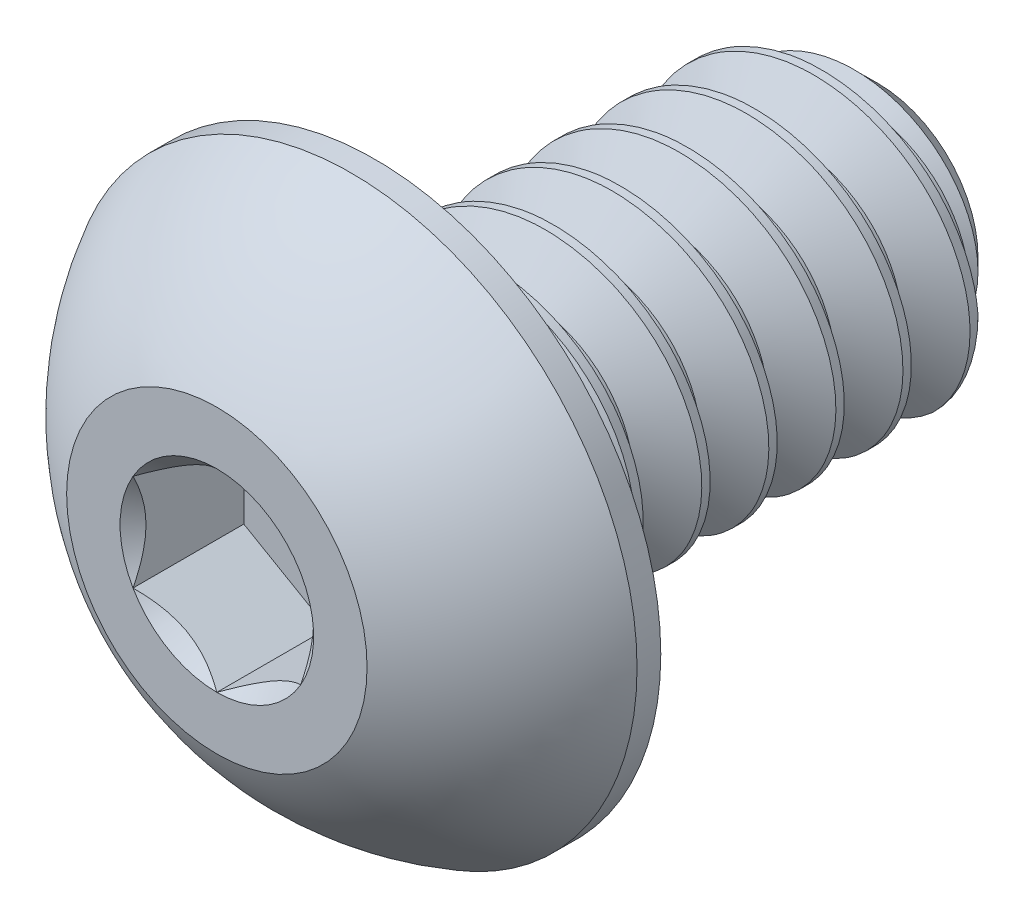
SolidWorks part; units mm, degrees
ref_plane "Front" through (0, 0, 0) normal (0, 0, 1) x (1, 0, 0)
ref_plane "Top" through (0, 0, 0) normal (0, 1, 0) x (1, 0, 0)
ref_plane "Right" through (0, 0, 0) normal (1, 0, 0) x (0, 0, -1)
sketch "Sketch1" plane through (0, 0, 0) normal (1, 0, 0) x (0, 0, -1)
  line L2 (1.4986, 1.4224) -> (6.2611, 1.4224)
  line L3 (6.2611, 1.4224) -> (6.2611, 0)
  line L4 (6.2611, 0) -> (1.4986, 0)
  line L6 (1.2738, 2.7051) -> (1.4986, 2.7051) construction
  line L7 (6.2611, 1.4224) -> (6.2611, -1.4224) construction
  line L8 (0, 0) -> (1.4986, 0) construction
  line L9 (1.4986, 2.7051) -> (1.4986, -2.7051) construction
  line L11 (1.4986, 1.4224) -> (1.4986, 0)
  line L13 (0, 0.7937) -> (0, -0.7937) construction
  line L14 (0, 0.7937) -> (0, 1.4224) construction
  arc A3 (0, 1.4224) -> (1.2738, 2.7051) centre (2.7151, 0) cw construction
  dimension "D1" = 0.2248
revolve "Revolve1" add sketch "Sketch1" angle 360 mid plane about L4
sketch "Sketch3" plane through (0, 0, -6.2611) normal (0, 0, -1) x (-1, 0, 0)
  circle A0 centre (0, 0) radius 1.4224
curve "Helix/Spiral1" pitch 0.635 height 5.3975 radius 1.4224 centre (0, 0, -6.2611) axis (0, 0, 1) start towards (0, 1, 0)
sketch "Sketch2" plane through (0, 0, 0) normal (1, 0, 0) x (0, 0, -1)
  line L0 (6.2611, 1.4224) -> (6.8167, 1.4224)
  line L1 (6.8167, 1.4224) -> (6.5786, 1.01)
  line L2 (6.5786, 1.01) -> (6.4992, 1.01)
  line L3 (6.4992, 1.01) -> (6.2611, 1.4224)
  line L4 (6.3802, 1.2162) -> (6.6977, 1.2162) construction
  dimension "D1" = 60
  dimension "D2" = 0.0794
  dimension "D3" = 0.3175
chamfer "Chamfer1" distance 0.4763 angle 45 1 edges at (0, 1.4224, -6.2611)
sweep "Cut-Sweep1" cut profiles "Sketch2" path "Helix/Spiral1" align with end faces yes
sketch "Sketch7" plane through (0, 0, 0) normal (1, 0, 0) x (0, 0, -1)
  line L6 (1.2738, 2.7051) -> (1.4986, 2.7051) construction
  line L8 (0, 0) -> (1.4986, 0) construction
  line L11 (1.4986, 2.7051) -> (1.4986, -2.7051) construction
  line L12 (1.2738, 2.7051) -> (1.4986, 2.7051)
  line L13 (0, 0) -> (1.4986, 0)
  line L14 (0, 0.7937) -> (0, -0.7937) construction
  line L15 (1.4986, 2.7051) -> (1.4986, 0)
  line L16 (0, 1.4224) -> (0, 0)
  arc A2 (1.2738, 2.7051) -> (0, 1.4224) centre (2.7151, 0) ccw construction
  arc A3 (1.2738, 2.7051) -> (0, 1.4224) centre (2.7151, 0) ccw
revolve "Revolve2" add sketch "Sketch7" angle 360 mid plane about L13
sketch "Sketch5" plane through (0, 0, 0) normal (0, 0, 1) x (1, 0, 0)
  line L1 (0.7937, -0.4583) -> (0.7937, 0.4583)
  line L2 (0.7937, 0.4583) -> (0, 0.9165)
  line L3 (0, 0.9165) -> (-0.7937, 0.4583)
  line L4 (-0.7937, 0.4583) -> (-0.7937, -0.4583)
  line L5 (-0.7937, -0.4583) -> (0, -0.9165)
  line L6 (0, -0.9165) -> (0.7937, -0.4583)
  circle A0 centre (0, 0) radius 0.7937 construction
extrude "Cut-Extrude2" cut sketch "Sketch5" against normal blind 1.049
sketch "Sketch6" plane through (0, 0, 0) normal (0, 0, 1) x (1, 0, 0)
  circle A0 centre (0, 0) radius 0.9165
extrude "Cut-Extrude3" cut sketch "Sketch6" against normal blind 1.049 draft 45
sketch "Sketch9" [suppressed] plane through (0, 0, -1.4986) normal (0, 0, 1) x (1, 0, 0)
  circle A2 centre (0, 0) radius 1.4224
extrude "Boss-Extrude2" [suppressed] add sketch "Sketch9" against normal offset from surface (12.7 mm away) 31.75 up to face at (0, 0.9461, -6.2611)
sketch "Sketch10" plane through (0, 0, 0) normal (1, 0, 0) x (0, 0, -1)
  line L0 (6.2611, 1.4224) -> (6.2611, -1.4224) construction
  point P0 (5.3086, -1.4224)
  dimension "D1" = 0.9525
equation "\"D3@Helix/Spiral1\" = \"Lg@Sketch1\" + \"D4@Helix/Spiral1\""
equation "\"D2@Sketch2\" = \"D4@Helix/Spiral1\" * .125"
equation "\"D3@Sketch2\" = \"D4@Helix/Spiral1\" * .5"
equation "\"D1@Chamfer1\" = \"D4@Helix/Spiral1\" * .75"
equation "\"D1@Cut-Extrude2\" = \"Head Ht@Sketch1\" * .7"
equation "\"D1@Sketch1\" = \"Head Ht@Sketch1\" * .15"
equation "\"D1@Sketch10\" = \"D4@Helix/Spiral1\" * 1.5"
equation "\"D1@Cut-Extrude3\" = \"D1@Cut-Extrude2\""
